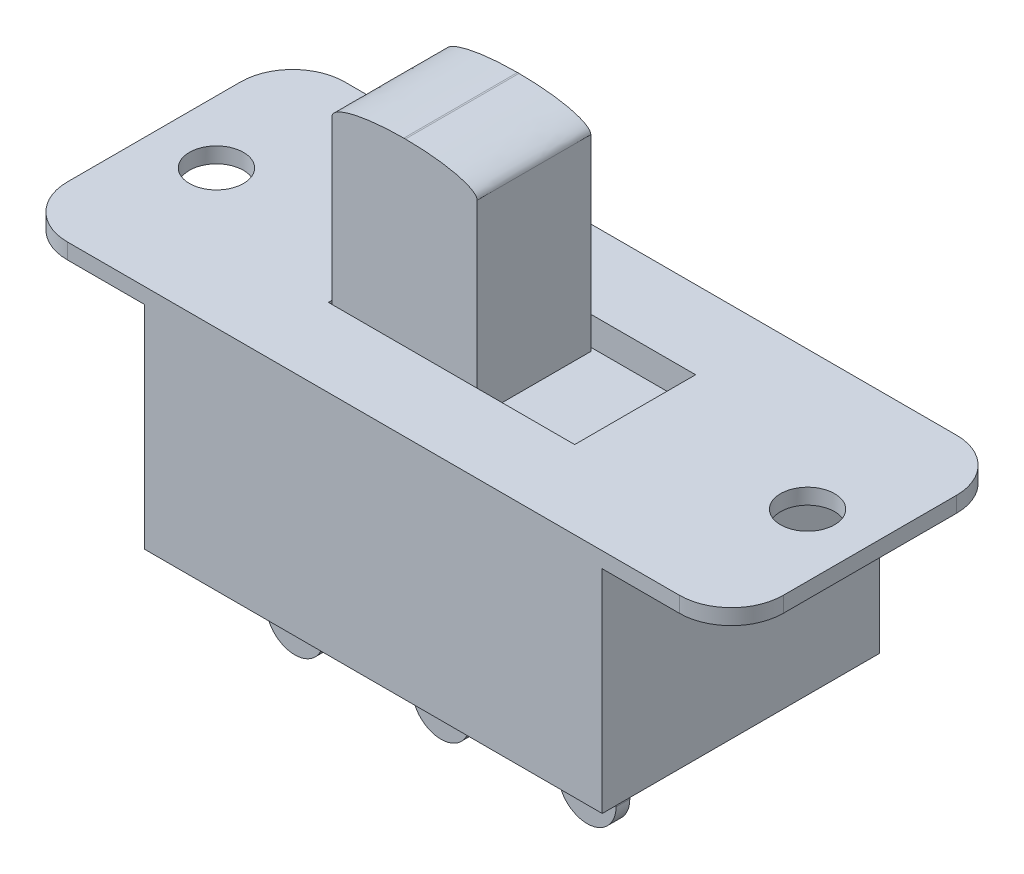
SolidWorks part; units mm, degrees
ref_plane "Front" through (0, 0, 0) normal (0, 0, 1) x (1, 0, 0)
ref_plane "Top" through (0, 0, 0) normal (0, 1, 0) x (1, 0, 0)
ref_plane "Right" through (0, 0, 0) normal (1, 0, 0) x (0, 0, -1)
sketch "Sketch1" plane through (0, 0, 0) normal (0, 1, 0) x (1, 0, 0)
  line L1 (2.54, 0) -> (32.4231, 0)
  line L2 (0, 2.54) -> (0, 10.9982)
  line L3 (2.54, 13.5382) -> (32.4231, 13.5382)
  line L4 (34.9631, 2.54) -> (34.9631, 10.9982)
  arc A0 (32.4231, 13.5382) -> (34.9631, 10.9982) centre (32.4231, 10.9982) cw
  arc A1 (32.4231, 0) -> (34.9631, 2.54) centre (32.4231, 2.54) ccw
  arc A2 (2.54, 0) -> (0, 2.54) centre (2.54, 2.54) cw
  arc A3 (0, 10.9982) -> (2.54, 13.5382) centre (2.54, 10.9982) cw
  point P7 (34.9631, 13.5382)
  point P12 (0, 0)
  point P15 (0, 13.5382)
  dimension "D3" = 2.54
  dimension "D1" = 34.9631
  dimension "D2" = 13.5382
extrude "Boss-Extrude1" add sketch "Sketch1" against normal blind 0.762
sketch "Sketch2" plane through (0, 0, 0) normal (0, 1, 0) x (1, 0, 0)
  line L0 (2.54, 0) -> (32.4231, 0) construction
  line L1 (6.3056, 0) -> (28.6576, 0)
  line L2 (6.3056, 0) -> (6.3056, 13.5382)
  line L3 (6.3056, 13.5382) -> (28.6576, 13.5382)
  line L4 (28.6576, 0) -> (28.6576, 13.5382)
  line L5 (32.4231, 13.5382) -> (2.54, 13.5382) construction
  point P8 (17.4816, 13.5382)
  dimension "D1" = 22.352
extrude "Boss-Extrude2" add sketch "Sketch2" against normal blind 11.1125
sketch "Sketch6" plane through (0, 0, 0) normal (0, 1, 0) x (1, 0, 0)
  line L1 (11.4681, 3.8164) -> (23.495, 3.8164)
  line L2 (11.4681, 3.8164) -> (11.4681, 9.7219)
  line L3 (11.4681, 9.7219) -> (23.495, 9.7219)
  line L4 (23.495, 3.8164) -> (23.495, 9.7219)
  line L5 (32.4231, 13.5382) -> (2.54, 13.5382) construction
  line L6 (0, 10.9982) -> (0, 2.54) construction
  point P6 (17.4816, 13.5382)
  point P7 (17.4816, 9.7219)
  point P8 (11.4681, 6.7691)
  point P11 (0, 6.7691)
  dimension "D1" = 12.0269
  dimension "D2" = 5.9055
extrude "Cut-Extrude2" cut sketch "Sketch6" against normal blind 1.397
sketch "Sketch3" plane through (0, 0, 0) normal (0, 1, 0) x (1, 0, 0)
  line L0 (11.4681, 9.7219) -> (11.4681, 3.8164) construction
  line L1 (11.4681, 9.5441) -> (18.5547, 9.5441)
  line L2 (11.4681, 9.5441) -> (11.4681, 3.9942)
  line L3 (11.4681, 3.9942) -> (18.5547, 3.9942)
  line L4 (18.5547, 9.5441) -> (18.5547, 3.9942)
  line L5 (0, 10.9982) -> (0, 2.54) construction
  line L6 (11.4681, 9.7219) -> (11.4681, 3.8164) construction
  point P4 (11.4681, 6.7691)
  point P7 (0, 6.7691)
  point P10 (11.4681, 6.7691)
  dimension "D1" = 7.0866
  dimension "D2" = 5.5499
extrude "Boss-Extrude3" add sketch "Sketch3" along normal blind 8.6106 and the other way up to next
fillet "Fillet4" radius 0.8382 2 edges at (18.5547, 8.6106, -6.7691) (11.4681, 8.6106, -6.7691) second distance 3.5052 first distance on face at (18.5547, 3.6068, -6.7691) first distance on face at (11.4681, 4.3053, -6.7691)
sketch "Sketch4" plane through (0, 0, 0) normal (0, 1, 0) x (1, 0, 0)
  line L0 (0, 10.9982) -> (0, 2.54) construction
  line L1 (34.9631, 2.54) -> (34.9631, 10.9982) construction
  circle A0 centre (3.048, 6.7691) radius 1.319
  circle A1 centre (31.9151, 6.7691) radius 1.319
  point P6 (0, 6.7691)
  dimension "D1" = 3.048
  dimension "D2" = 3.048
extrude "Cut-Extrude1" cut sketch "Sketch4" against normal through all
sketch "Sketch5" plane through (0, -11.1125, 0) normal (0, -1, 0) x (1, 0, 0)
  line L0 (6.3056, 0) -> (28.6576, 0) construction
  line L1 (8.9345, -3.302) -> (11.7539, -3.302)
  line L2 (8.9345, -3.302) -> (8.9345, -3.9751)
  line L3 (8.9345, -3.9751) -> (11.7539, -3.9751)
  line L4 (11.7539, -3.302) -> (11.7539, -3.9751)
  line L5 (16.0719, -3.302) -> (18.8913, -3.302)
  line L6 (16.0719, -3.302) -> (16.0719, -3.9751)
  line L7 (16.0719, -3.9751) -> (18.8913, -3.9751)
  line L8 (18.8913, -3.302) -> (18.8913, -3.9751)
  line L9 (23.2093, -3.302) -> (26.0287, -3.302)
  line L10 (23.2093, -3.302) -> (23.2093, -3.9751)
  line L11 (23.2093, -3.9751) -> (26.0287, -3.9751)
  line L12 (26.0287, -3.302) -> (26.0287, -3.9751)
  point P14 (17.4816, 0)
  point P15 (17.4816, -3.302)
  dimension "D1" = 2.8194
  dimension "D2" = 0.6731
  dimension "D3" = 3.302
  dimension "D4" = 4.318
  dimension "D5" = 4.318
extrude "Boss-Extrude4" add sketch "Sketch5" along normal blind 4.1021
fillet "Fillet5" 2 edges at (8.9345, -15.2146, -3.6385) (11.7539, -15.2146, -3.6385) type full round first side face at (8.9345, -13.1635, -3.6385) second side face at (11.7539, -13.1635, -3.6385) middle face at (10.3442, -15.2146, -3.6385)
fillet "Fillet6" 2 edges at (16.0719, -15.2146, -3.6385) (18.8913, -15.2146, -3.6385) type full round first side face at (16.0719, -13.1635, -3.6385) second side face at (18.8913, -13.1635, -3.6385) middle face at (17.4816, -15.2146, -3.6385)
fillet "Fillet7" 2 edges at (23.2093, -15.2146, -3.6385) (26.0287, -15.2146, -3.6385) type full round first side face at (23.2093, -13.1635, -3.6385) second side face at (26.0287, -13.1635, -3.6385) middle face at (24.619, -15.2146, -3.6385)
